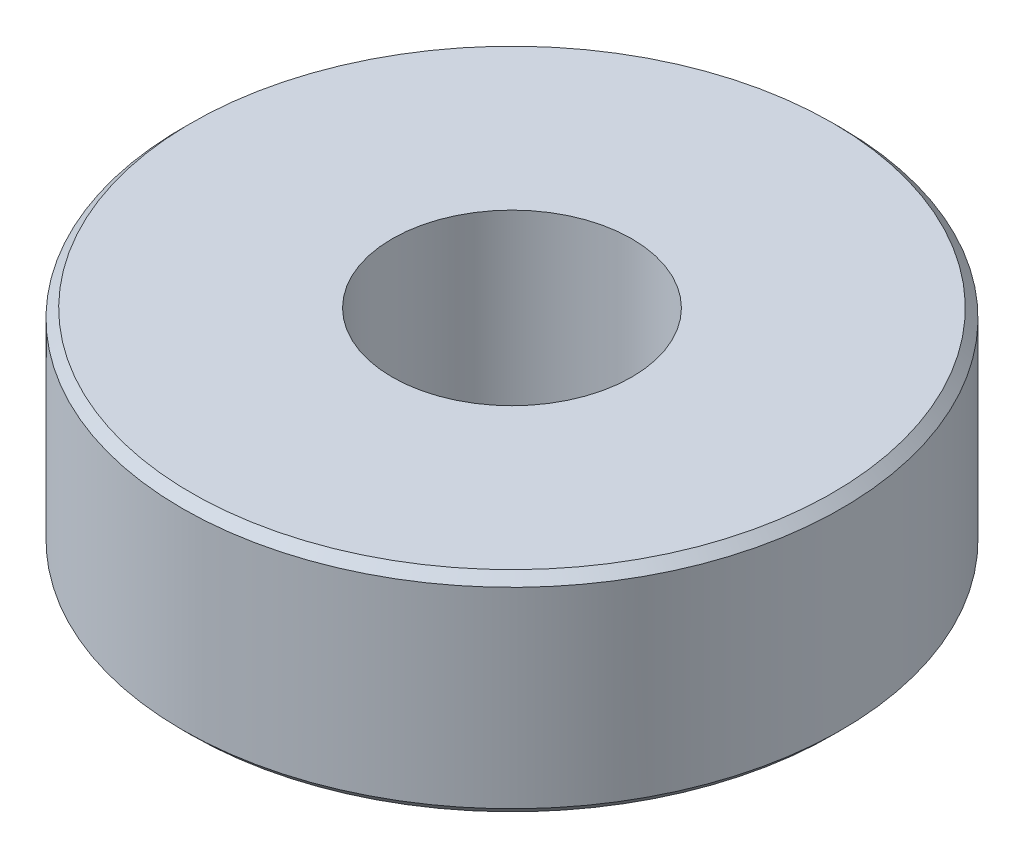
SolidWorks part; units mm, degrees
ref_plane "Front Plane" through (0, 0, 0) normal (0, 0, 1) x (1, 0, 0)
ref_plane "Top Plane" through (0, 0, 0) normal (0, 1, 0) x (1, 0, 0)
ref_plane "Right Plane" through (0, 0, 0) normal (1, 0, 0) x (0, 0, -1)
sketch "Sketch1" plane through (0, 0, 0) normal (0, 1, 0) x (1, 0, 0)
  circle A0 centre (0, 0) radius 4
  circle A1 centre (0, 0) radius 11
  dimension "D1" = 8
  dimension "D2" = 22
extrude "Boss-Extrude1" add sketch "Sketch1" along normal blind 3.5 and the other way blind 3.5
chamfer "Chamfer1" distance 0.3 angle 45 2 edges at (0, -3.5, 11) (0, 3.5, 11)
